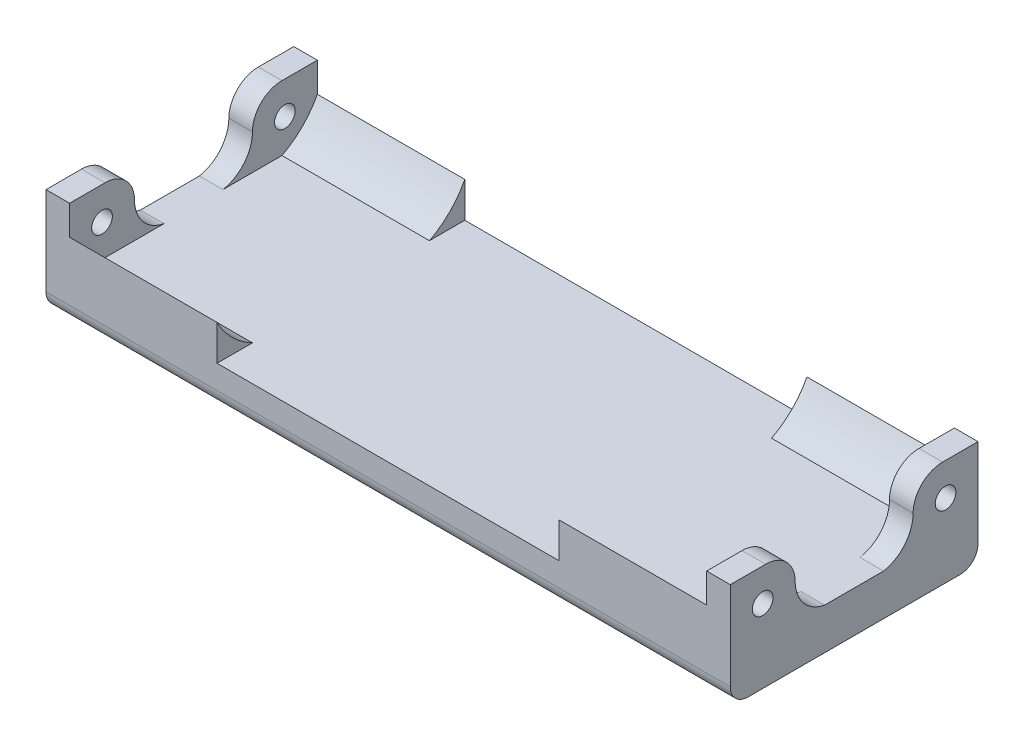
SolidWorks part; units mm, degrees
ref_plane "Front Plane" through (0, 0, 0) normal (0, 0, 1) x (1, 0, 0)
ref_plane "Top Plane" through (0, 0, 0) normal (0, 1, 0) x (1, 0, 0)
ref_plane "Right Plane" through (0, 0, 0) normal (1, 0, 0) x (0, 0, -1)
sketch "Sketch1" plane through (0, 0, 0) normal (0, 1, 0) x (1, 0, 0)
  line L1 (-58, -21) -> (58, -21)
  line L2 (-58, -21) -> (-58, 21)
  line L3 (-58, 21) -> (58, 21)
  line L4 (58, -21) -> (58, 21)
  line L5 (-58, -21) -> (58, 21) construction
  line L6 (-58, 21) -> (58, -21) construction
  point P0 (0, 0)
  dimension "D1" = 42
  dimension "D2" = 116
extrude "Boss-Extrude1" add sketch "Sketch1" along normal blind 7
sketch "Sketch2" plane through (0, 0, 0) normal (1, 0, 0) x (0, 0, -1)
  line L0 (-21, 7) -> (21, 7) construction
  line L1 (-21, 7) -> (21, 7)
  line L2 (0, 0) -> (0, 30.7392) construction
  line L3 (-21, 7) -> (-21, 54.5)
  line L4 (21, 7) -> (21, 54.5)
  line L5 (21, 48.95) -> (-21, 48.95)
  line L6 (21, 30.75) -> (-29.0104, 30.75) construction
  line L7 (21, 7) -> (10, 7)
  line L8 (21, 7) -> (21, 18)
  line L9 (21, 18) -> (15, 18)
  line L11 (10, 7) -> (0, 7)
  line L12 (-21, 18) -> (-15, 18)
  arc A0 (15, 18) -> (10, 13) centre (15, 13) ccw
  arc A1 (10, 13) -> (5, 7) centre (3.9, 13) cw
  arc A2 (-10, 13) -> (-5, 7) centre (-3.9, 13) ccw
  arc A3 (-15, 18) -> (-10, 13) centre (-15, 13) cw
  point P16 (10, 18)
  line B0 (-25, 54.5) -> (-25, 39.5)
  line B1 (25, 54.5) -> (-25, 54.5)
  line B2 (25, 54.5) -> (25, 39.5)
  line B3 (25, 7) -> (25, 39.5)
  line B4 (25, 7) -> (-25, 7)
  line B5 (-25, 7) -> (-25, 39.5)
  circle B6 centre (-15.5, 43.475) radius 1.75
  circle B7 centre (15.5, 43.475) radius 1.75
  circle B8 centre (15.5, 12.475) radius 1.75
  circle B9 centre (0, 27.975) radius 11.075
  circle B10 centre (-15.5, 12.475) radius 1.75
  dimension "D3" = 5
  dimension "D1" = 41.95
  dimension "D2" = 11
sketch_block_instance "Block1-2"
sketch_block "Block1"
extrude "Boss-Extrude2" add sketch "Sketch2" along normal up to surface and the other way up to surface contours A0 A1 L11 L1 L4 L9 B8 | A3 L12 L3 L1 A2 B10 region at (0, 12.5, 20.8058) region at (0, 8.9706, -8.7353) up to face at (58, 3.5, 0) other way up to face at (-58, 3.5, 0)
extrude "Cut-Extrude1" cut sketch "Sketch2<3>" against normal mid plane 108 contours A0 A1 L11 L1 L4 L9 B8 | A3 L12 L3 L1 A2 B10 region at (0, 12.5, 20.8058) region at (0, 8.9706, -8.7353)
sketch "Sketch2<3>" plane through (0, 0, 0) normal (1, 0, 0) x (0, 0, -1) same geometry as "Sketch2"
sketch "Sketch3" plane through (-54, 0, 0) normal (1, 0, 0) x (0, 0, -1)
  line L0 (-21, 7) -> (-15, 7)
  line L1 (-21, 7) -> (-21, 13)
  line L2 (-21, 18) -> (-21, 0) construction
  line L3 (0, 0) -> (0, 17.1319) construction
  line L4 (21, 7) -> (21, 13)
  line L5 (21, 7) -> (15, 7)
  arc A0 (-15, 7) -> (-21, 13) centre (-8.566, 19.434) cw
  arc A1 (15, 7) -> (21, 13) centre (8.566, 19.434) ccw
  dimension "D3" = 14
  dimension "D1" = 6
  dimension "D2" = 6
extrude "Boss-Extrude3" add sketch "Sketch3" along normal blind 25
mirror "Mirror4" about plane through (0, 0, 0) normal (1, 0, 0) of "Boss-Extrude3"
fillet "Fillet1" radius 3 2 edges at (0, 0, 21) (0, 0, -21)
